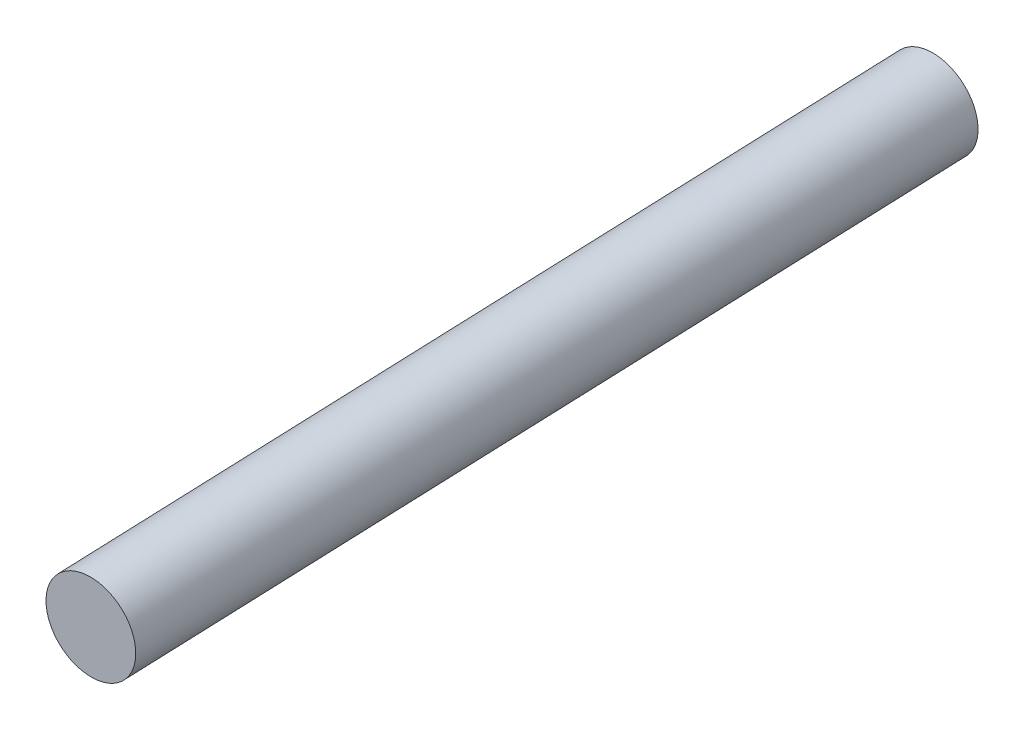
SolidWorks part; units mm, degrees
ref_plane "Front Plane" through (0, 0, 0) normal (0, 0, 1) x (1, 0, 0)
ref_plane "Top Plane" through (0, 0, 0) normal (0, 1, 0) x (1, 0, 0)
ref_plane "Right Plane" through (0, 0, 0) normal (1, 0, 0) x (0, 0, -1)
sketch3d "3DSketch1"
  line L0 (-1565.7546, 2102.6584, -729.0934) -> (-1521.3046, 1646.4842, -899.7331) construction
  line L1 (-1781.6546, 2063.3353, -1077.804) -> (-1565.7546, 2063.3353, -1077.804) construction
  line L2 (-1781.6546, 2076.3795, -1099.5987) -> (-1781.6546, 2050.2911, -1056.0093) construction
  line L3 (-1565.7546, 2063.3353, -1077.804) -> (-1561.1375, 2055.2752, -746.8179)
  line L4 (-1521.3046, 1640.4773, -883.6748) -> (-1521.3046, 1652.4911, -915.7914) construction
  circle A2 centre (-1565.7546, 2102.6584, -729.0934) radius 17.145 construction
  point P4 (-1564.1963, 2086.6666, -735.0754)
  dimension "D1" = 215.9
  dimension "D2" = 50.8
sweep "Sweep1" add path "3DSketch1" circular profile diameter 34.29 parameters "D3"=34.29
